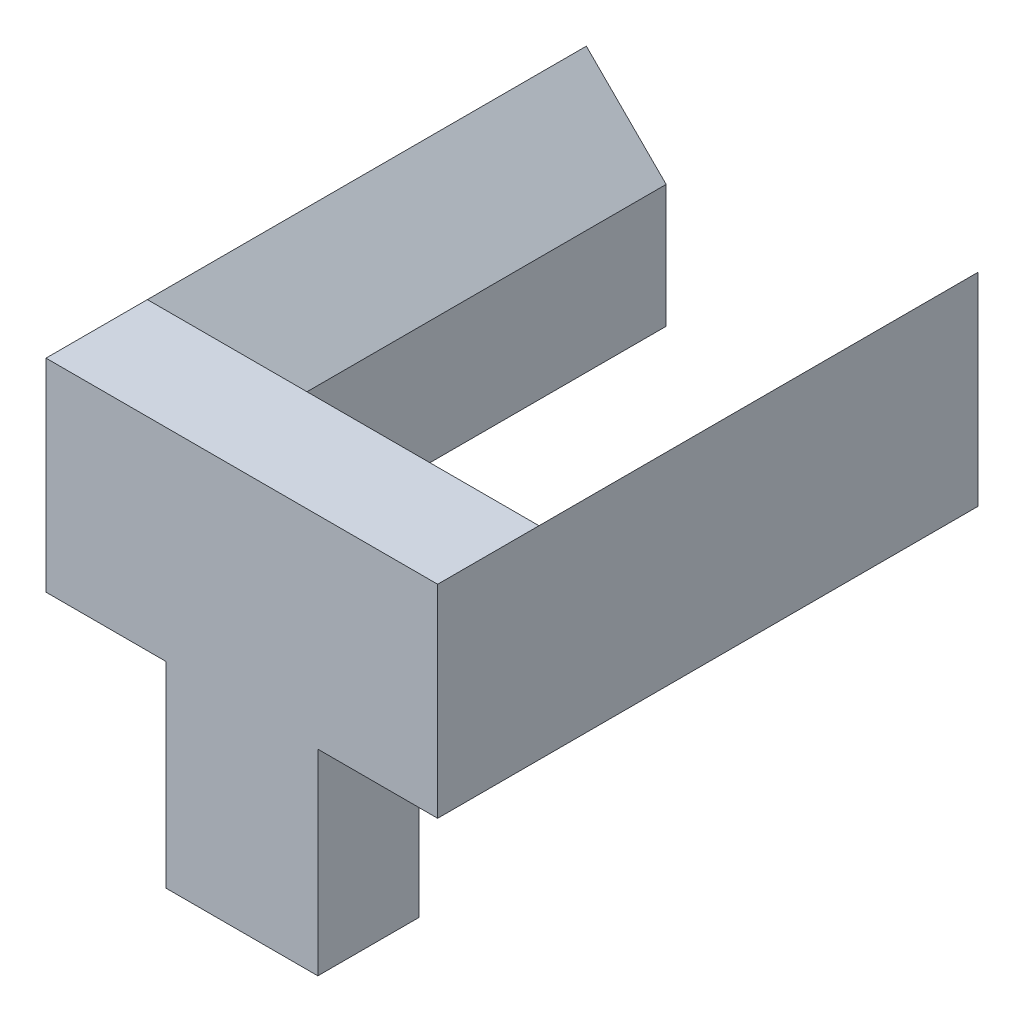
SolidWorks part; units mm, degrees
ref_plane "Front Plane" through (0, 0, 0) normal (0, 0, 1) x (1, 0, 0)
ref_plane "Top Plane" through (0, 0, 0) normal (0, 1, 0) x (1, 0, 0)
ref_plane "Right Plane" through (0, 0, 0) normal (1, 0, 0) x (0, 0, -1)
sketch "Sketch1" plane through (0, 0, 0) normal (0, 1, 0) x (1, 0, 0)
  line L0 (-13.9881, 12.8425) -> (-13.9881, -12.5575)
  line L1 (-13.9881, -12.5575) -> (24.1119, -12.5575)
  line L2 (24.1119, -12.5575) -> (24.1119, 12.8425)
  line L3 (24.1119, 12.8425) -> (-13.9881, 12.8425)
  line L4 (5.0619, 12.8425) -> (5.0619, -12.5575) construction
extrude "Boss-Extrude1" add sketch "Sketch1" along normal blind 99.9998 contours L3 L0 L1 L2
sketch "Sketch2" plane through (24.1119, 0, 0) normal (1, 0, 0) x (0, 0, -1)
  line L0 (-12.5575, 99.9998) -> (12.8425, 99.9998)
  line L1 (12.8425, 99.9998) -> (12.8425, 49.1998)
  line L2 (12.8425, 99.9998) -> (12.8425, 0) construction
  line L3 (12.8425, 49.1998) -> (-12.5575, 49.1998)
  line L4 (-12.5575, 99.9998) -> (-12.5575, 0) construction
  line L5 (-12.5575, 49.1998) -> (-12.5575, 99.9998)
extrude "Boss-Extrude2" add sketch "Sketch2" along normal blind 30.0228 contours L1 L3 L5 L0
sketch "Sketch3" plane through (-13.9881, 0, 0) normal (-1, 0, 0) x (0, 0, 1)
  line L0 (12.5575, 99.9998) -> (12.5575, 0) construction
  line L1 (-12.8425, 99.9998) -> (12.5575, 99.9998)
  line L2 (-12.8425, 99.9998) -> (-12.8425, 49.1998)
  line L3 (-12.8425, 49.1998) -> (12.5575, 49.1998)
  line L4 (12.5575, 99.9998) -> (12.5575, 49.1998)
extrude "Boss-Extrude3" add sketch "Sketch3" along normal blind 30.0228
sketch "Sketch4" plane through (0, 0, -12.8425) normal (0, 0, -1) x (-1, 0, 0)
  line L0 (-54.1347, 99.9998) -> (-54.1347, 49.1998)
  line L4 (-36.1667, 79.9998) -> (-54.1347, 99.9998)
  line L5 (-36.1667, 79.9998) -> (-36.1667, 49.1998)
  line L6 (-54.1347, 49.1998) -> (-24.1119, 49.1998) construction
  line L7 (-36.1667, 49.1998) -> (-54.1347, 49.1998)
extrude "Boss-Extrude4" add sketch "Sketch4" along normal blind 110.0074
sketch "Sketch5" plane through (0, 0, -12.8425) normal (0, 0, -1) x (-1, 0, 0)
  line L0 (44.0109, 99.9998) -> (44.0109, 49.1998)
  line L1 (44.0109, 49.1998) -> (24.0109, 49.1998)
  line L2 (44.0109, 49.1998) -> (13.9881, 49.1998) construction
  line L3 (24.0109, 49.1998) -> (24.0109, 79.9998)
  line L4 (24.0109, 79.9998) -> (44.0109, 99.9998)
extrude "Boss-Extrude5" add sketch "Sketch5" along normal blind 110.0074 contours L4 L0 L1 L3
sketch "Sketch8" plane through (0, 0, 0) normal (0, -1, 0) x (1, 0, 0)
  line L0 (5.0619, 12.5575) -> (5.0619, -12.8425) construction
  line L1 (-13.9881, 12.5575) -> (24.1119, 12.5575) construction
  line L2 (24.1119, -12.8425) -> (-13.9881, -12.8425) construction
  line L3 (5.0619, -0.1425) -> (15.0619, -0.1425) construction
  line L4 (5.0619, -0.1425) -> (-4.9381, -0.1425) construction
  circle A0 centre (-4.9381, -0.1425) radius 3.81
  circle A1 centre (15.0619, -0.1425) radius 3.81
  dimension "D1" = 7.62
  dimension "D2" = 7.62
extrude "Cut-Extrude1" cut sketch "Sketch8" against normal blind 25.4
